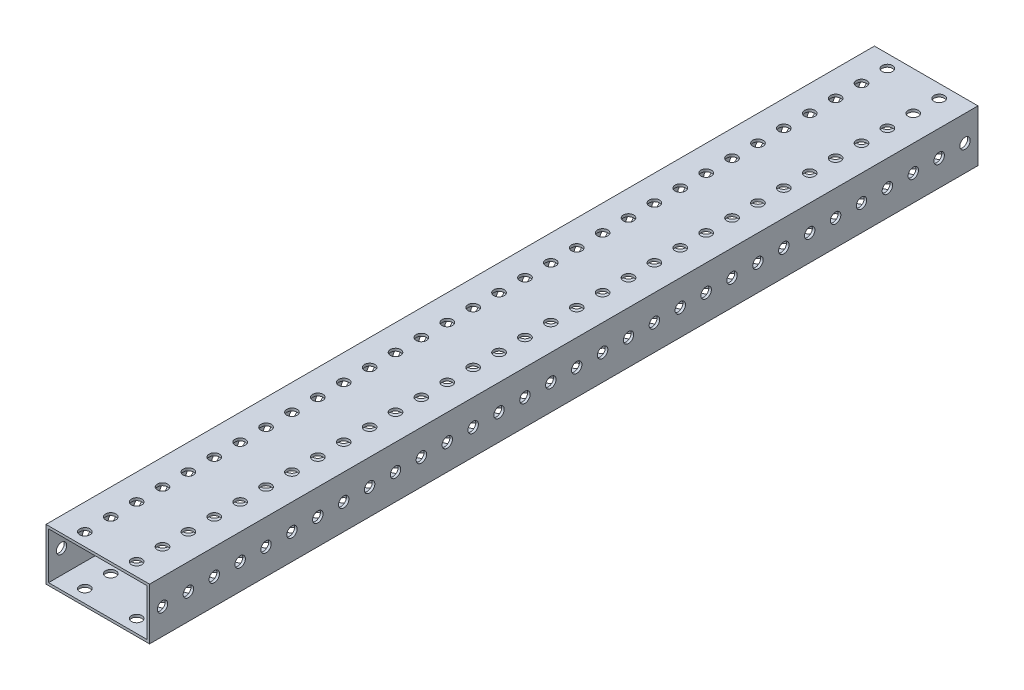
SolidWorks part; units mm, degrees
ref_plane "Front Plane" through (0, 0, 0) normal (0, 0, 1) x (1, 0, 0)
ref_plane "Top Plane" through (0, 0, 0) normal (0, 1, 0) x (1, 0, 0)
ref_plane "Right Plane" through (0, 0, 0) normal (1, 0, 0) x (0, 0, -1)
sketch "Sketch1" plane through (0, 0, 0) normal (0, 1, 0) x (1, 0, 0)
  line L1 (0, 0) -> (50.8, 0)
  line L2 (0, 0) -> (0, 406.4)
  line L3 (0, 406.4) -> (50.8, 406.4)
  line L4 (50.8, 0) -> (50.8, 406.4)
  dimension "D1" = 50.8
  dimension "D2" = 406.4
extrude "Boss-Extrude1" add sketch "Sketch1" along normal blind 25.4
sketch "Sketch2" plane through (0, 0, 0) normal (0, 0, 1) x (1, 0, 0)
  line L0 (0, 25.4) -> (50.8, 25.4) construction
  line L3 (1.27, 1.27) -> (49.53, 1.27)
  line L4 (1.27, 1.27) -> (1.27, 24.13)
  line L5 (1.27, 24.13) -> (49.53, 24.13)
  line L6 (49.53, 1.27) -> (49.53, 24.13)
  line L7 (0, 25.4) -> (0, 0) construction
  point P8 (25.4, 12.7)
  dimension "D1" = 48.26
  dimension "D2" = 1.27
  dimension "D3" = 22.86
  dimension "D4" = 1.27
extrude "Cut-Extrude1" cut sketch "Sketch2" against normal through all
sketch "Sketch4" plane through (0, 25.4, 0) normal (0, 1, 0) x (1, 0, 0)
  line L0 (0, 0) -> (50.8, 0) construction
  line L1 (0, 406.4) -> (0, 0) construction
  line L2 (50.8, 0) -> (50.8, 406.4) construction
  circle A0 centre (12.7, 6.35) radius 2.5527
  circle A1 centre (38.1, 6.35) radius 2.5527
  circle A2 centre (12.7, 19.05) radius 2.5527
  circle A3 centre (38.1, 19.05) radius 2.5527
  circle A4 centre (12.7, 31.75) radius 2.5527
  circle A5 centre (38.1, 31.75) radius 2.5527
  circle A6 centre (12.7, 44.45) radius 2.5527
  circle A7 centre (38.1, 44.45) radius 2.5527
  circle A8 centre (12.7, 57.15) radius 2.5527
  circle A9 centre (38.1, 57.15) radius 2.5527
  circle A10 centre (12.7, 69.85) radius 2.5527
  circle A11 centre (38.1, 69.85) radius 2.5527
  circle A12 centre (12.7, 82.55) radius 2.5527
  circle A13 centre (38.1, 82.55) radius 2.5527
  circle A14 centre (12.7, 95.25) radius 2.5527
  circle A15 centre (38.1, 95.25) radius 2.5527
  circle A16 centre (12.7, 107.95) radius 2.5527
  circle A17 centre (38.1, 107.95) radius 2.5527
  circle A18 centre (12.7, 120.65) radius 2.5527
  circle A19 centre (38.1, 120.65) radius 2.5527
  circle A20 centre (12.7, 133.35) radius 2.5527
  circle A21 centre (38.1, 133.35) radius 2.5527
  circle A22 centre (12.7, 146.05) radius 2.5527
  circle A23 centre (38.1, 146.05) radius 2.5527
  circle A24 centre (12.7, 158.75) radius 2.5527
  circle A25 centre (38.1, 158.75) radius 2.5527
  circle A26 centre (12.7, 171.45) radius 2.5527
  circle A27 centre (38.1, 171.45) radius 2.5527
  circle A28 centre (12.7, 184.15) radius 2.5527
  circle A29 centre (38.1, 184.15) radius 2.5527
  circle A30 centre (12.7, 196.85) radius 2.5527
  circle A31 centre (38.1, 196.85) radius 2.5527
  circle A32 centre (12.7, 209.55) radius 2.5527
  circle A33 centre (38.1, 209.55) radius 2.5527
  circle A34 centre (12.7, 222.25) radius 2.5527
  circle A35 centre (38.1, 222.25) radius 2.5527
  circle A36 centre (12.7, 234.95) radius 2.5527
  circle A37 centre (38.1, 234.95) radius 2.5527
  circle A38 centre (12.7, 247.65) radius 2.5527
  circle A39 centre (38.1, 247.65) radius 2.5527
  circle A40 centre (12.7, 260.35) radius 2.5527
  circle A41 centre (38.1, 260.35) radius 2.5527
  circle A42 centre (12.7, 273.05) radius 2.5527
  circle A43 centre (38.1, 273.05) radius 2.5527
  circle A44 centre (12.7, 285.75) radius 2.5527
  circle A45 centre (38.1, 285.75) radius 2.5527
  circle A46 centre (12.7, 298.45) radius 2.5527
  circle A47 centre (38.1, 298.45) radius 2.5527
  circle A48 centre (12.7, 311.15) radius 2.5527
  circle A49 centre (38.1, 311.15) radius 2.5527
  circle A50 centre (12.7, 323.85) radius 2.5527
  circle A51 centre (38.1, 323.85) radius 2.5527
  circle A52 centre (12.7, 336.55) radius 2.5527
  circle A53 centre (38.1, 336.55) radius 2.5527
  circle A54 centre (12.7, 349.25) radius 2.5527
  circle A55 centre (38.1, 349.25) radius 2.5527
  circle A56 centre (12.7, 361.95) radius 2.5527
  circle A57 centre (38.1, 361.95) radius 2.5527
  circle A58 centre (12.7, 374.65) radius 2.5527
  circle A59 centre (38.1, 374.65) radius 2.5527
  circle A60 centre (12.7, 387.35) radius 2.5527
  circle A61 centre (38.1, 387.35) radius 2.5527
  circle A62 centre (12.7, 400.05) radius 2.5527
  circle A63 centre (38.1, 400.05) radius 2.5527
  circle A64 centre (12.7, 412.75) radius 2.5527
  circle A65 centre (38.1, 412.75) radius 2.5527
  circle A66 centre (12.7, 425.45) radius 2.5527
  circle A67 centre (38.1, 425.45) radius 2.5527
  circle A68 centre (12.7, 438.15) radius 2.5527
  circle A69 centre (38.1, 438.15) radius 2.5527
  circle A70 centre (12.7, 450.85) radius 2.5527
  circle A71 centre (38.1, 450.85) radius 2.5527
  circle A72 centre (12.7, 463.55) radius 2.5527
  circle A73 centre (38.1, 463.55) radius 2.5527
  circle A74 centre (12.7, 476.25) radius 2.5527
  circle A75 centre (38.1, 476.25) radius 2.5527
  circle A76 centre (12.7, 488.95) radius 2.5527
  circle A77 centre (38.1, 488.95) radius 2.5527
  circle A78 centre (12.7, 501.65) radius 2.5527
  circle A79 centre (38.1, 501.65) radius 2.5527
  dimension "D1" = 6.35
  dimension "D2" = 6.35
  dimension "D3" = 5.1054
  dimension "D4" = 5.1054
  dimension "D5" = 12.7
  dimension "D6" = 12.7
  dimension "D8" = 12.7
  dimension "D7" = 40
sketch "Sketch5" plane through (0, 0, 0) normal (-1, 0, 0) x (0, 0, 1)
  line L0 (-406.4, 0) -> (0, 0) construction
  line L1 (0, 25.4) -> (0, 0) construction
  circle A0 centre (-6.35, 12.7) radius 2.5527
  circle A1 centre (-19.05, 12.7) radius 2.5527
  circle A2 centre (-31.75, 12.7) radius 2.5527
  circle A3 centre (-44.45, 12.7) radius 2.5527
  circle A4 centre (-57.15, 12.7) radius 2.5527
  circle A5 centre (-69.85, 12.7) radius 2.5527
  circle A6 centre (-82.55, 12.7) radius 2.5527
  circle A7 centre (-95.25, 12.7) radius 2.5527
  circle A8 centre (-107.95, 12.7) radius 2.5527
  circle A9 centre (-120.65, 12.7) radius 2.5527
  circle A10 centre (-133.35, 12.7) radius 2.5527
  circle A11 centre (-146.05, 12.7) radius 2.5527
  circle A12 centre (-158.75, 12.7) radius 2.5527
  circle A13 centre (-171.45, 12.7) radius 2.5527
  circle A14 centre (-184.15, 12.7) radius 2.5527
  circle A15 centre (-196.85, 12.7) radius 2.5527
  circle A16 centre (-209.55, 12.7) radius 2.5527
  circle A17 centre (-222.25, 12.7) radius 2.5527
  circle A18 centre (-234.95, 12.7) radius 2.5527
  circle A19 centre (-247.65, 12.7) radius 2.5527
  circle A20 centre (-260.35, 12.7) radius 2.5527
  circle A21 centre (-273.05, 12.7) radius 2.5527
  circle A22 centre (-285.75, 12.7) radius 2.5527
  circle A23 centre (-298.45, 12.7) radius 2.5527
  circle A24 centre (-311.15, 12.7) radius 2.5527
  circle A25 centre (-323.85, 12.7) radius 2.5527
  circle A26 centre (-336.55, 12.7) radius 2.5527
  circle A27 centre (-349.25, 12.7) radius 2.5527
  circle A28 centre (-361.95, 12.7) radius 2.5527
  circle A29 centre (-374.65, 12.7) radius 2.5527
  circle A30 centre (-387.35, 12.7) radius 2.5527
  circle A31 centre (-400.05, 12.7) radius 2.5527
  circle A32 centre (-412.75, 12.7) radius 2.5527
  circle A33 centre (-425.45, 12.7) radius 2.5527
  circle A34 centre (-438.15, 12.7) radius 2.5527
  circle A35 centre (-450.85, 12.7) radius 2.5527
  circle A36 centre (-463.55, 12.7) radius 2.5527
  circle A37 centre (-476.25, 12.7) radius 2.5527
  circle A38 centre (-488.95, 12.7) radius 2.5527
  circle A39 centre (-501.65, 12.7) radius 2.5527
  dimension "D1" = 12.7
  dimension "D2" = 6.35
  dimension "D3" = 5.1054
  dimension "D5" = 12.7
  dimension "D4" = 40
extrude "Cut-Extrude2" cut sketch "Sketch4" against normal through all
extrude "Cut-Extrude3" cut sketch "Sketch5" against normal through all
